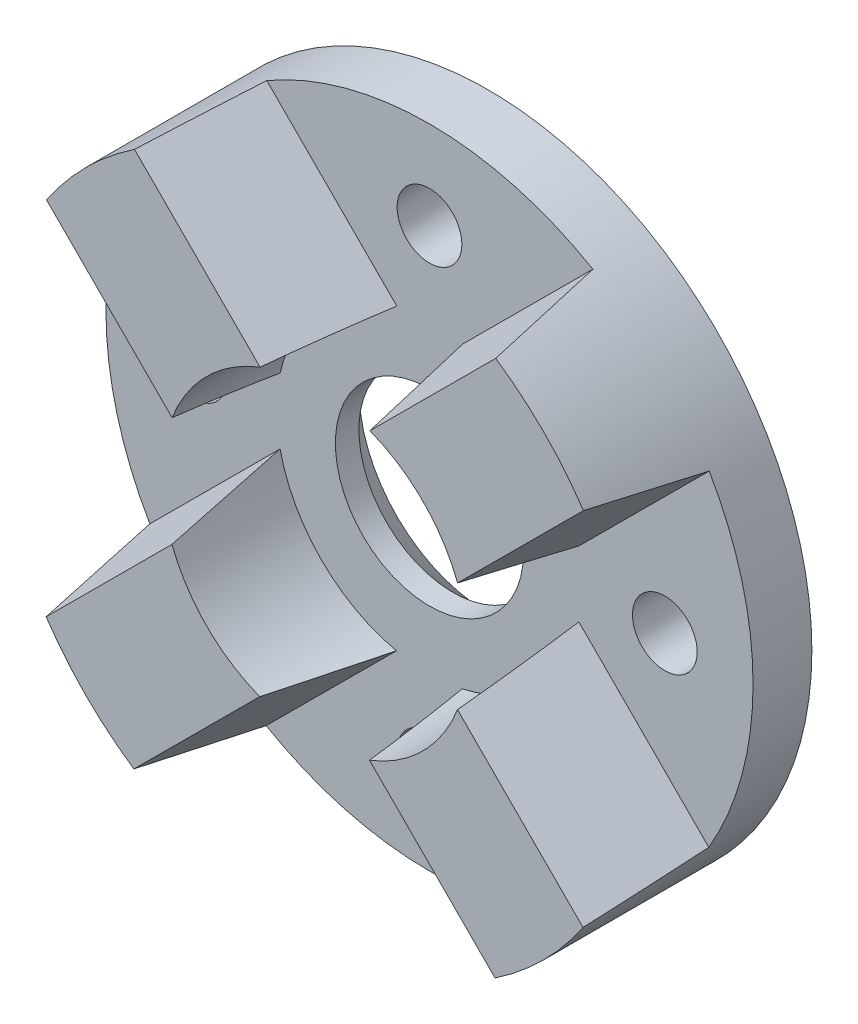
SolidWorks part; units mm, degrees
material "ABS"
ref_plane "Płaszczyzna przednia" through (0, 0, 0) normal (0, 0, 1) x (1, 0, 0)
ref_plane "Płaszczyzna górna" through (0, 0, 0) normal (0, 1, 0) x (1, 0, 0)
ref_plane "Płaszczyzna prawa" through (0, 0, 0) normal (1, 0, 0) x (0, 0, -1)
sketch "Szkic1" plane through (0, 0, 0) normal (0, 0, 1) x (1, 0, 0)
  circle A0 centre (0, 0) radius 11
  circle A1 centre (0, 0) radius 8 construction
  circle A2 centre (0, 8) radius 1.1
  circle A3 centre (8, 0) radius 1.1
  circle A4 centre (0, -8) radius 1.1
  circle A5 centre (-8, 0) radius 1.1
  circle A6 centre (0, 0) radius 3.2
  point P15 (0, 0)
  dimension "D1" = 22
  dimension "D2" = 16
  dimension "D3" = 2.2
  dimension "D5" = 6.4
  dimension "D4" = 4
extrude "Dodanie-wyciągnięcie1" add sketch "Szkic1" along normal blind 2
chamfer "Sfazowanie1" distance 1.2 angle 45 1 edges at (3.2, 0, 0)
sketch "Szkic2" plane through (0, 0, 2) normal (0, 0, 1) x (1, 0, 0)
  line L0 (-3.6722, -3.6817) -> (-7.7782, -7.7782)
  line L1 (-4.8106, -1.9744) -> (-9.0699, -6.2239)
  line L2 (-1.9854, -4.806) -> (-6.2447, -9.0556)
  circle A0 centre (0, 0) radius 11 construction
  circle A1 centre (0, 0) radius 11
  circle A2 centre (0, 0) radius 3.2 construction
  circle A3 centre (0, 0) radius 3.2
  circle A4 centre (0, 0) radius 5.2
  point P12 (0, 0)
  point P13 (0, 0)
  circle M7 centre (0, 0) radius 3.2
  circle M8 centre (0, 0) radius 11
  dimension "D1" = 4
  dimension "D2" = 2
extrude "Dodanie-wyciągnięcie2" add sketch "Szkic2" along normal blind 3.9 contours L1 L0 M7 M8 | L2 L0 M7 M8
chamfer "Sfazowanie2" distance 0.8 angle 80 2 edges at (-4.1151, -6.9308, 2) (-6.9403, -4.0991, 2)
pattern_circular "Szyk kołowy1" count 4 every 90 about axis through (0, 0, 0) along (0, 0, 1) of "Sfazowanie2", "Dodanie-wyciągnięcie2"
